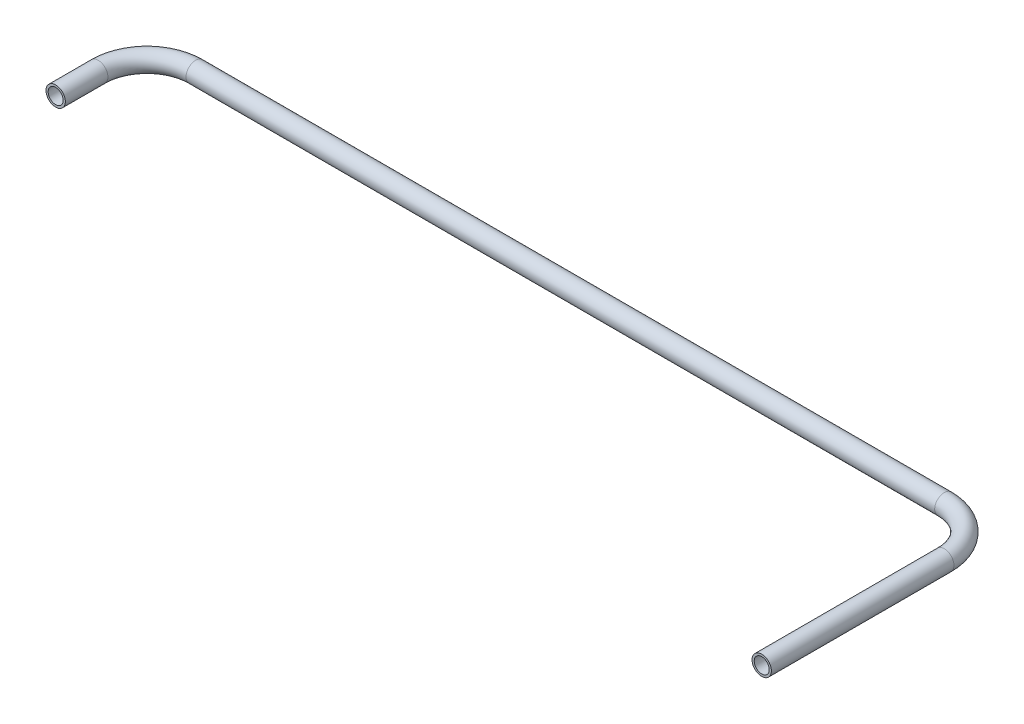
SolidWorks part; units mm, degrees
ref_plane "Front Plane" through (0, 0, 0) normal (0, 0, 1) x (1, 0, 0)
ref_plane "Top Plane" through (0, 0, 0) normal (0, 1, 0) x (1, 0, 0)
ref_plane "Right Plane" through (0, 0, 0) normal (1, 0, 0) x (0, 0, -1)
sketch "Sketch1" plane through (0, 0, 0) normal (0, 1, 0) x (1, 0, 0)
  line L0 (0, 0) -> (0, 14)
  line L1 (16, 30) -> (262, 30)
  line L2 (278, 14) -> (278, -46)
  arc A0 (262, 30) -> (278, 14) centre (262, 14) cw
  arc A1 (0, 14) -> (16, 30) centre (16, 14) cw
  dimension "D1" = 16
  dimension "D2" = 16
  dimension "D3" = 14
  dimension "D4" = 60
  dimension "D5" = 278
sketch "Sketch2" plane through (0, 0, 0) normal (0, 0, 1) x (1, 0, 0)
  circle A0 centre (0, 0) radius 3.175
  dimension "D1" = 6.35
sweep "Sweep-Thin1" add profiles "Sketch2" path "Sketch1" parameters "D1"=0.7112
